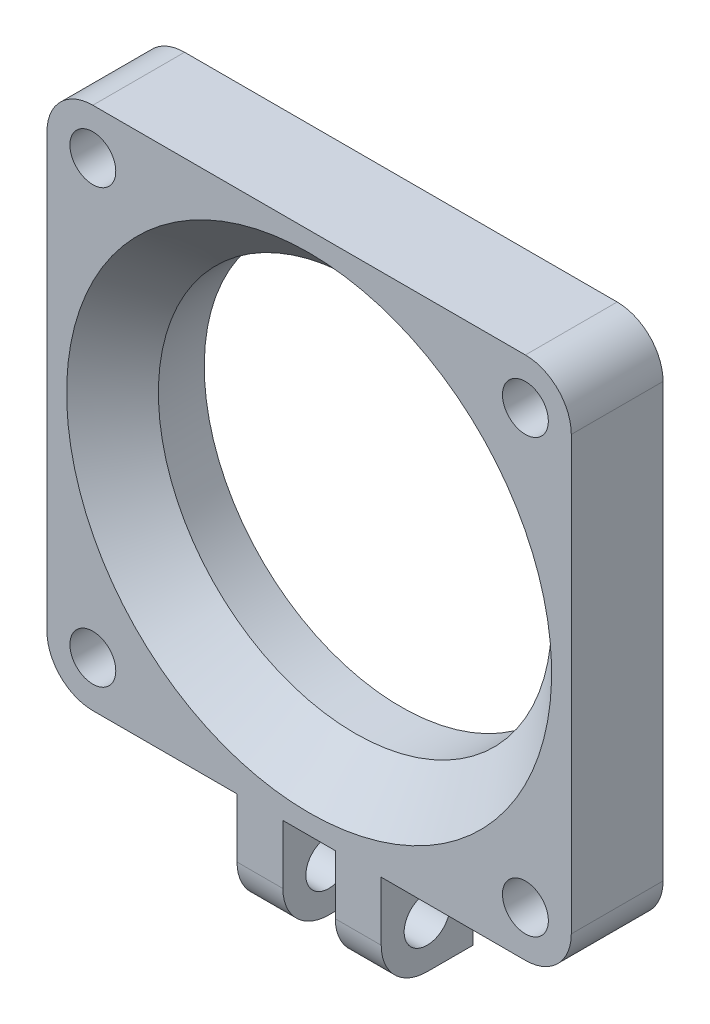
SolidWorks part; units mm, degrees
ref_plane "Front Plane" through (0, 0, 0) normal (0, 0, 1) x (1, 0, 0)
ref_plane "Top Plane" through (0, 0, 0) normal (0, 1, 0) x (1, 0, 0)
ref_plane "Right Plane" through (0, 0, 0) normal (1, 0, 0) x (0, 0, -1)
sketch "Sketch1" plane through (0, 0, 0) normal (0, 1, 0) x (1, 0, 0)
  line L1 (-16.5, 20) -> (16.5, 20)
  line L2 (-20, 16.5) -> (-20, -16.5)
  line L3 (-16.5, -20) -> (16.5, -20)
  line L4 (20, 16.5) -> (20, -16.5)
  line L5 (-20, 20) -> (20, -20) construction
  line L6 (-20, -20) -> (20, 20) construction
  arc A0 (-20, -16.5) -> (-16.5, -20) centre (-16.5, -16.5) ccw
  arc A1 (16.5, -20) -> (20, -16.5) centre (16.5, -16.5) ccw
  arc A2 (16.5, 20) -> (20, 16.5) centre (16.5, 16.5) cw
  arc A3 (-16.5, 20) -> (-20, 16.5) centre (-16.5, 16.5) ccw
  point P0 (0, 0)
  dimension "D1" = 3.5
  dimension "D2" = 40
  dimension "D3" = 40
extrude "Boss-Extrude1" add sketch "Sketch1" along normal blind 7
sketch "Sketch3" plane through (0, 7, 0) normal (0, 1, 0) x (1, 0, 0)
  line L0 (0, 20) -> (0, -20) construction
  line L1 (16.5, 20) -> (-16.5, 20) construction
  line L2 (-16.5, -20) -> (16.5, -20) construction
  line L3 (-20, 0) -> (20, 0) construction
  line L4 (-20, 16.5) -> (-20, -16.5) construction
  line L5 (20, -16.5) -> (20, 16.5) construction
  circle A1 centre (-16.5, 16.5) radius 1.75
  circle A2 centre (16.5, 16.5) radius 1.75
  circle A3 centre (16.5, -16.5) radius 1.75
  circle A4 centre (-16.5, -16.5) radius 1.75
  dimension "D1" = 3.5
extrude "Cut-Extrude2" cut sketch "Sketch3" against normal up to next
sketch "Sketch7" plane through (0, 0, 0) normal (0, -1, 0) x (1, 0, 0)
  line L0 (0, 0) -> (0, 20) construction
  line L1 (-16.5, 20) -> (16.5, 20) construction
  line L2 (-20, 0) -> (20, 0) construction
  line L3 (-20, -16.5) -> (-20, 16.5) construction
  line L4 (20, 16.5) -> (20, -16.5) construction
  line L5 (5.5, 0) -> (5.5, 28)
  line L6 (-2, 0) -> (-5.5, 0)
  line L7 (-2, 0) -> (-2, 28)
  line L8 (-2, 28) -> (-5.5, 28)
  line L9 (-5.5, 0) -> (-5.5, 28)
  line L10 (2, 28) -> (5.5, 28)
  line L11 (2, 0) -> (2, 28)
  line L12 (2, 0) -> (5.5, 0)
  dimension "D1" = 3.5
  dimension "D2" = 8
  dimension "D3" = 4
extrude "Boss-Extrude2" add sketch "Sketch7" against normal blind 7
sketch "Sketch8" plane through (5.5, 0, 0) normal (1, 0, 0) x (0, 0, -1)
  line L0 (-20, 7) -> (-28, 7) construction
  line L2 (-28, 7) -> (-28, 0) construction
  line L3 (-24.5, 7) -> (-28, 7)
  line L4 (-28, 7) -> (-28, 3.5)
  line L5 (-28, 7) -> (-28, 0) construction
  arc A0 (-24.5, 7) -> (-28, 3.5) centre (-24.5, 3.5) ccw
  point P7 (-28, 3.5)
  line M4 (-20, 7) -> (-28, 7)
  line M5 (-28, 7) -> (-28, 0)
extrude "Cut-Extrude3" cut sketch "Sketch8" against normal through all contours A0 M4 M5 region at (5.5, 6.2182, 27.2182)
sketch "Sketch9" plane through (5.5, 0, 0) normal (1, 0, 0) x (0, 0, -1)
  circle A0 centre (-24.5, 3.5) radius 1.75
  arc A1 (-24.5, 7) -> (-28, 3.5) centre (-24.5, 3.5) ccw construction
  dimension "D1" = 3.5
extrude "Cut-Extrude4" cut sketch "Sketch9" against normal through all
sketch "Sketch13" plane through (0, 0, 0) normal (0, -1, 0) x (1, 0, 0)
  line L0 (-20, 0) -> (20, 0) construction
  line L1 (-20, -16.5) -> (-20, 16.5) construction
  line L2 (20, 16.5) -> (20, -16.5) construction
  line L3 (0, -20) -> (0, 20) construction
  line L4 (16.5, -20) -> (-16.5, -20) construction
  line L5 (-2, 20) -> (2, 20) construction
  circle A0 centre (0, 0) radius 15
  dimension "D1" = 30
extrude "Cut-Extrude5" cut sketch "Sketch13" against normal through all
ref_axis "Axis3" through (0, 7, 0) along (0, -1, 0)
ref_plane "Plane2" through (0, 0, 0) normal (1, 0, 0) x (0, 0, -1)
sketch "Sketch14" plane through (0, 0, 0) normal (1, 0, 0) x (0, 0, -1)
  line L0 (0, 0) -> (0, 7)
  line L1 (0, 7) -> (0, 0) construction
  line L2 (0, 7) -> (18.5, 7)
  line L3 (-16.5, 7) -> (16.5, 7) construction
  line L4 (18.5, 7) -> (15, 3.5)
  line L5 (15, 3.5) -> (15, 0)
  line L6 (-16.5, 0) -> (16.5, 0) construction
  line L7 (15, 0) -> (0, 0)
  line L8 (-15, 0) -> (15, 0) construction
  line L9 (15, 7) -> (-15, 7) construction
  point P16 (15, 0)
  dimension "D1" = 3.5
  dimension "D2" = 45
revolve "Cut-Revolve1" cut sketch "Sketch14" angle 360 about axis through (0, 7, 0) along (0, -1, 0)
move or copy body "Body-Move/Copy1" bodies to move or copy 112 copy no rotation origin (0, 3.5, 4) rotation axis (1, 0, 0) rotation angle 90
